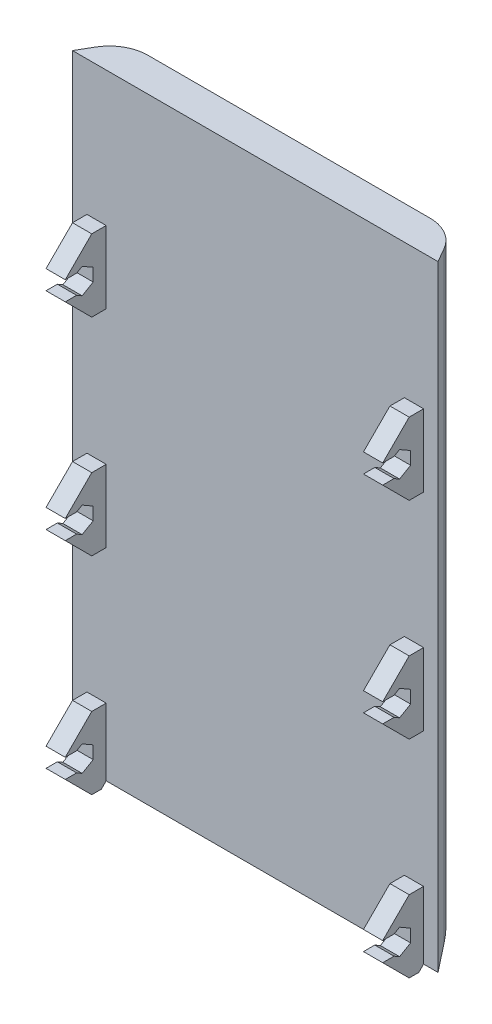
SolidWorks part; units mm, degrees
ref_plane "Front Plane" through (0, 0, 0) normal (0, 0, 1) x (1, 0, 0)
ref_plane "Top Plane" through (0, 0, 0) normal (0, 1, 0) x (1, 0, 0)
ref_plane "Right Plane" through (0, 0, 0) normal (1, 0, 0) x (0, 0, -1)
sketch "Sketch1" plane through (0, 0, 0) normal (0, 1, 0) x (1, 0, 0)
  line L0 (-9.2151, 0) -> (-9.2151, -10)
  line L1 (-9.2151, -10) -> (-5.2151, -10)
  line L2 (-5.2151, -10) -> (-5.2151, 0)
  line L3 (-5.2151, 0) -> (56.7849, 0)
  line L4 (56.7849, 0) -> (56.7849, -10)
  line L5 (56.7849, -10) -> (60.7849, -10)
  line L6 (60.7849, -10) -> (60.7849, 0)
  line L7 (60.7849, 0) -> (63.7849, 0)
  line L8 (-9.2151, 0) -> (-12.2151, 0)
  line L9 (-12.2151, 0) -> (-8.1737, 7)
  line L10 (-8.1737, 7) -> (59.7434, 7)
  line L11 (59.7434, 7) -> (63.7849, 0)
  line L12 (25.7849, 7) -> (25.7849, 0) construction
  dimension "D1" = 3
  dimension "D2" = 10
  dimension "D3" = 70
  dimension "D4" = 7
  dimension "D5" = 4
  dimension "D6" = 60
extrude "Boss-Extrude1" add sketch "Sketch1" along normal blind 129
sketch "Sketch4" plane through (60.7849, 0, 0) normal (1, 0, 0) x (0, 0, -1)
  line L0 (0, 129) -> (0, 0) construction
  line L1 (-37.5185, 129) -> (0, 129)
  line L2 (-37.5185, 129) -> (-37.5185, 101)
  line L3 (-37.5185, 101) -> (0, 101)
  line L4 (0, 129) -> (0, 101)
  line L5 (-37.5185, 129) -> (0, 101) construction
  line L6 (-37.5185, 101) -> (0, 129) construction
  line L7 (-10, 129) -> (0, 129) construction
  point P0 (-18.7592, 115)
  dimension "D1" = 28
extrude "Cut-Extrude1" cut sketch "Sketch4" against normal through all
sketch "Sketch5" plane through (60.7849, 0, 0) normal (1, 0, 0) x (0, 0, -1)
  line L0 (0, 129) -> (0, 0) construction
  line L1 (-33.3149, 86) -> (0, 86)
  line L2 (-33.3149, 86) -> (-33.3149, 58)
  line L3 (-33.3149, 58) -> (0, 58)
  line L4 (0, 86) -> (0, 58)
  line L5 (-33.3149, 86) -> (0, 58) construction
  line L6 (-33.3149, 58) -> (0, 86) construction
  line L7 (-10, 101) -> (0, 101) construction
  point P0 (-16.6574, 72)
  dimension "D1" = 28
  dimension "D2" = 15
extrude "Cut-Extrude2" cut sketch "Sketch5" against normal through all
sketch "Sketch6" plane through (0, 0, 0) normal (1, 0, 0) x (0, 0, -1)
  line L0 (-10, 101) -> (-10, 86) construction
  line L1 (-2.7, 94.8279) -> (-5, 96.1558)
  line L2 (-5, 96.1558) -> (-7.3, 94.8279)
  line L3 (-7.3, 94.8279) -> (-7.3, 92.1721)
  line L4 (-7.3, 92.1721) -> (-5, 90.8442)
  line L5 (-5, 90.8442) -> (-2.7, 92.1721)
  line L6 (-2.7, 92.1721) -> (-2.7, 94.8279)
  line L7 (-10, 101) -> (0, 101) construction
  line L8 (-6.15, 95.4919) -> (-10, 95.4919)
  line L9 (-6.15, 91.5081) -> (-10, 91.5081)
  line L10 (-10, 91.5081) -> (-10, 95.4919)
  circle A1 centre (-5, 93.5) radius 2.3 construction
  dimension "D1" = 4.6
  dimension "D2" = 7.5
  dimension "D3" = 5
extrude "Cut-Extrude3" cut sketch "Sketch6" against normal through all and the other way through all contours L10 L9 L4 L3 L2 L8 | L5 L6 L1 L2 L3 L4 region at (0, 93.5, 5) region at (0, 93.5, 8.5351)
pattern_linear "LPattern1" count 4 spacing 43 along (0, -1, 0) of "Cut-Extrude2", "Cut-Extrude3"
chamfer "Chamfer6" distance 8 angle 45 1 edges at (25.7849, 0, -7)
fillet "Fillet1" radius 8 2 edges at (-8.1737, 68.5, -7) (59.7434, 68.5, -7)
chamfer "Chamfer5" distance 7 angle 45 12 edges at (58.7849, 101, 10) (58.7849, 86, 10) (-7.2151, 101, 10) (-7.2151, 86, 10) (-7.2151, 58, 10) (-7.2151, 43, 10) (58.7849, 58, 10) (58.7849, 43, 10) (58.7849, 15, 10) (58.7849, 0, 10) (-7.2151, 0, 10) (-7.2151, 15, 10)
